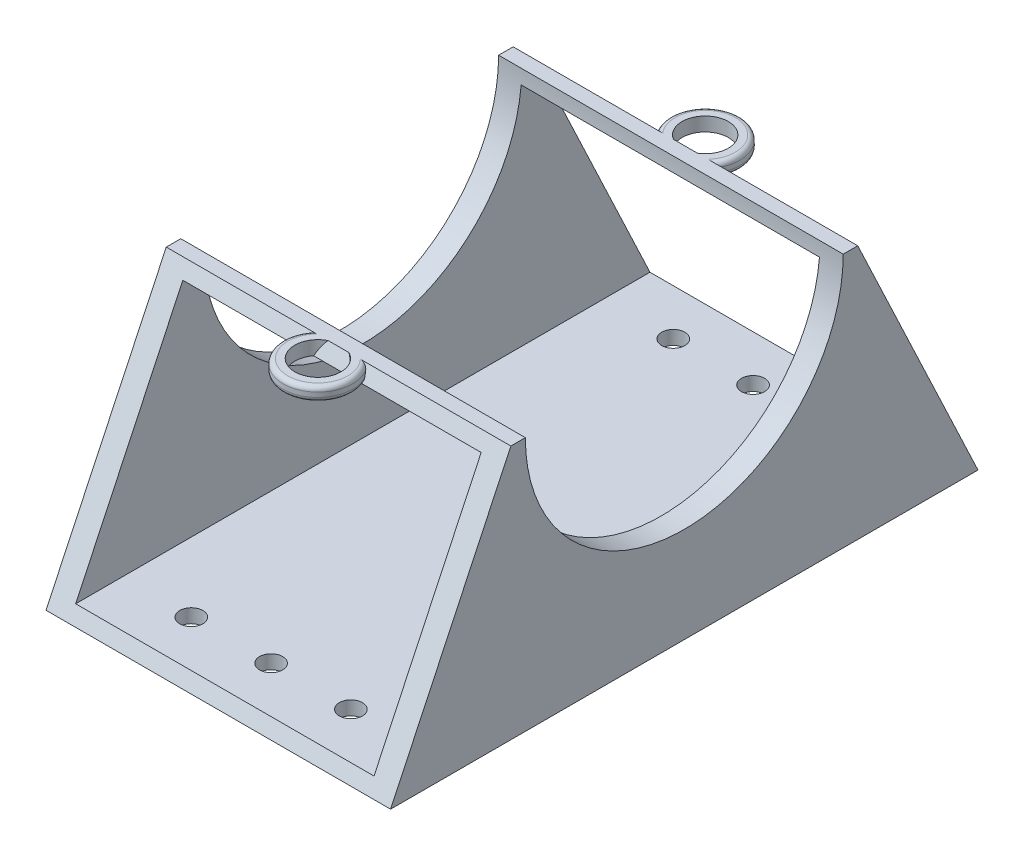
SolidWorks part; units mm, degrees
ref_plane "Front Plane" through (0, 0, 0) normal (0, 0, 1) x (1, 0, 0)
ref_plane "Top Plane" through (0, 0, 0) normal (0, 1, 0) x (1, 0, 0)
ref_plane "Right Plane" through (0, 0, 0) normal (1, 0, 0) x (0, 0, -1)
sketch "Sketch1" plane through (0, 0, 0) normal (0, 1, 0) x (1, 0, 0)
  line L1 (-37.25, -37.5) -> (37.25, -37.5)
  line L2 (-37.25, -37.5) -> (-37.25, 37.5)
  line L3 (-37.25, 37.5) -> (37.25, 37.5)
  line L4 (37.25, -37.5) -> (37.25, 37.5)
  line L5 (-37.25, -37.5) -> (37.25, 37.5) construction
  line L6 (-37.25, 37.5) -> (37.25, -37.5) construction
  point P0 (0, 0)
  dimension "D1" = 74.5
  dimension "D2" = 75
extrude "Boss-Extrude1" add sketch "Sketch1" along normal blind 55
ref_plane "Plane1" through (0, 0, -37.5) normal (0, 0, -1) x (-1, 0, 0)
ref_plane "Plane2" through (0, 0, 37.5) normal (0, 0, 1) x (1, 0, 0)
ref_plane "Plane3" through (-37.25, 0, 0) normal (-1, 0, 0) x (0, 0, 1)
ref_plane "Plane4" through (37.25, 0, 0) normal (1, 0, 0) x (0, 0, -1)
sketch "Sketch5" plane through (37.25, 0, 0) normal (1, 0, 0) x (0, 0, -1)
  line L1 (-37.5, 55) -> (37.5, 55) construction
  circle A0 centre (0, 55) radius 34.3616
  point P2 (0, 55)
  dimension "D1" = 68.7231
extrude "Cut-Extrude2" cut sketch "Sketch5" against normal through all
sketch "Sketch7" plane through (37.25, 0, 0) normal (1, 0, 0) x (0, 0, -1)
  line L0 (-37.5, 55) -> (-63.5, 0)
  line L1 (-63.5, 0) -> (-37.5, 0)
  line L2 (-37.5, 0) -> (-37.5, 55)
  dimension "D1" = 26
extrude "Boss-Extrude3" add sketch "Sketch7" against normal blind 74.5
sketch "Sketch8" plane through (37.25, 0, 0) normal (1, 0, 0) x (0, 0, -1)
  line L0 (37.5, 55) -> (63.5, 0)
  line L1 (63.5, 0) -> (37.5, 0)
  line L2 (37.5, 0) -> (37.5, 55)
  dimension "D1" = 26
extrude "Boss-Extrude4" add sketch "Sketch8" against normal blind 74.5
sketch "Sketch9" plane through (0, 0, 37.5) normal (0, 0, 1) x (1, 0, 0)
  line L0 (-37.25, 55) -> (37.25, 55) construction
  line L1 (-32.25, 3) -> (32.25, 3)
  line L2 (-32.25, 3) -> (-32.25, 52)
  line L3 (-32.25, 52) -> (32.25, 52)
  line L4 (32.25, 3) -> (32.25, 52)
  line L5 (-32.25, 3) -> (32.25, 52) construction
  line L6 (-32.25, 52) -> (32.25, 3) construction
  line L7 (-37.25, 0) -> (37.25, 0) construction
  line L8 (37.25, 55) -> (37.25, 0) construction
  line L9 (-37.25, 55) -> (-37.25, 0) construction
  point P0 (0, 27.5)
  dimension "D1" = 3
  dimension "D2" = 3
  dimension "D3" = 5
  dimension "D4" = 5
extrude "Cut-Extrude3" cut sketch "Sketch9" against normal through all both and the other way through all
sketch "Sketch10" plane through (0, 55, 0) normal (0, 1, 0) x (1, 0, 0)
  circle A0 centre (0, 41.7725) radius 7.5
  circle A1 centre (0, 41.7725) radius 5
  line M4 (37.25, 37.5) -> (-37.25, 37.5)
  dimension "D1" = 15
  dimension "D2" = 10
extrude "Boss-Extrude5" add sketch "Sketch10" against normal blind 3 contours A1 A0 M4 region at (6.9762, 55, -39.5912)
sketch "Sketch11" plane through (0, 55, 0) normal (0, 1, 0) x (1, 0, 0)
  circle A0 centre (0, -41.9683) radius 7.5
  circle A1 centre (0, -41.9683) radius 5
  point P3 (0, -30.2849)
  line M10 (-37.25, -37.5) -> (37.25, -37.5)
  dimension "D1" = 15
  dimension "D2" = 10
extrude "Boss-Extrude6" add sketch "Sketch11" against normal blind 3 contours A1 A0 M10 region at (-2.2927, 55, 48.9075)
fillet "Fillet1" radius 1 4 edges at (0, 52, 49.4683) (0, 55, 49.4683) (0, 52, -49.2725) (0, 55, -49.2725)
sketch "Sketch12" plane through (0, 3, 0) normal (0, 1, 0) x (1, 0, 0)
  line L0 (-32.25, 62.0818) -> (-32.25, -62.0818) construction
  line L1 (32.25, 62.0818) -> (32.25, -62.0818) construction
  line L2 (-32.25, -62.0818) -> (32.25, -62.0818) construction
  circle A0 centre (-17.25, -52.0818) radius 2.5
  circle A1 centre (17.25, -52.0818) radius 2.5
  circle A2 centre (0, -52.0818) radius 2.5
  dimension "D1" = 5
  dimension "D3" = 5
  dimension "D4" = 15
  dimension "D5" = 10
  dimension "D6" = 10
  dimension "D7" = 5
  dimension "D8" = 10
  dimension "D9" = 17.25
  dimension "D2" = 15
extrude "Cut-Extrude4" cut sketch "Sketch12" against normal through all
pattern_linear "LPattern1" count 2 spacing 104.2 along (0, 0, -1) of "Cut-Extrude4"
